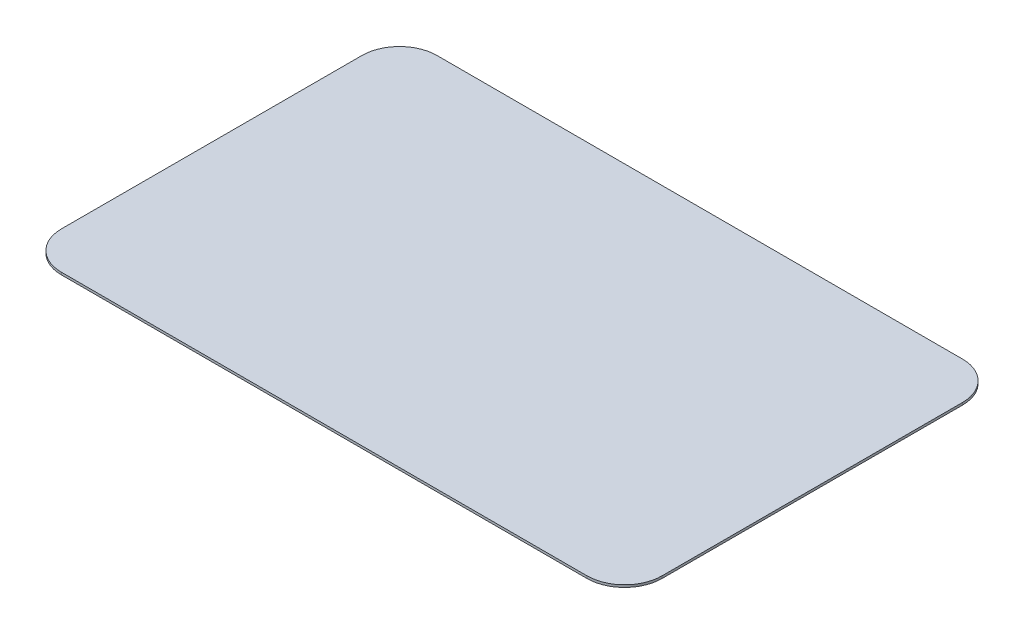
SolidWorks part; units mm, degrees
ref_plane "Front Plane" through (0, 0, 0) normal (0, 0, 1) x (1, 0, 0)
ref_plane "Top Plane" through (0, 0, 0) normal (0, 1, 0) x (1, 0, 0)
ref_plane "Right Plane" through (0, 0, 0) normal (1, 0, 0) x (0, 0, -1)
ref_plane "SheetPlane" through (0, -26.0848, 0) normal (0, -1, 0) x (-1, 0, 0)
sketch "Sketch1" plane through (0, -26.0848, 0) normal (0, -1, 0) x (-1, 0, 0)
  line L12 (-151.5596, 85.5327) -> (-151.5292, -16.0673) construction
  line L13 (38.9366, 98.2896) -> (-138.8634, 98.2364) construction
  line L14 (51.6708, -16.0066) -> (51.6404, 85.5934) construction
  line L15 (-138.8254, -28.7635) -> (38.9746, -28.7104) construction
  line L16 (-151.5596, 85.5327) -> (-151.5292, -16.0673)
  line L17 (38.9366, 98.2896) -> (-138.8634, 98.2364)
  line L18 (51.6708, -16.0066) -> (51.6404, 85.5934)
  line L19 (-138.8254, -28.7635) -> (38.9746, -28.7104)
  arc A12 (-151.5292, -16.0673) -> (-138.8254, -28.7635) centre (-138.8292, -16.0635) ccw construction
  arc A13 (-138.8634, 98.2364) -> (-151.5596, 85.5327) centre (-138.8596, 85.5365) ccw construction
  arc A14 (51.6404, 85.5934) -> (38.9366, 98.2896) centre (38.9404, 85.5896) ccw construction
  arc A15 (38.9746, -28.7104) -> (51.6708, -16.0066) centre (38.9708, -16.0104) ccw construction
  arc A16 (-151.5292, -16.0673) -> (-138.8254, -28.7635) centre (-138.8292, -16.0635) ccw
  arc A17 (-138.8634, 98.2364) -> (-151.5596, 85.5327) centre (-138.8596, 85.5365) ccw
  arc A18 (51.6404, 85.5934) -> (38.9366, 98.2896) centre (38.9404, 85.5896) ccw
  arc A19 (38.9746, -28.7104) -> (51.6708, -16.0066) centre (38.9708, -16.0104) ccw
extrude "MainBody" add sketch "Sketch1" along normal blind 0.7937
equation "\"SheetThickness\"= 0.03125in"
equation "\"D1@MainBody\" = \"SheetThickness\""
equation "\"SheetTolerance\"= 0.012in"
